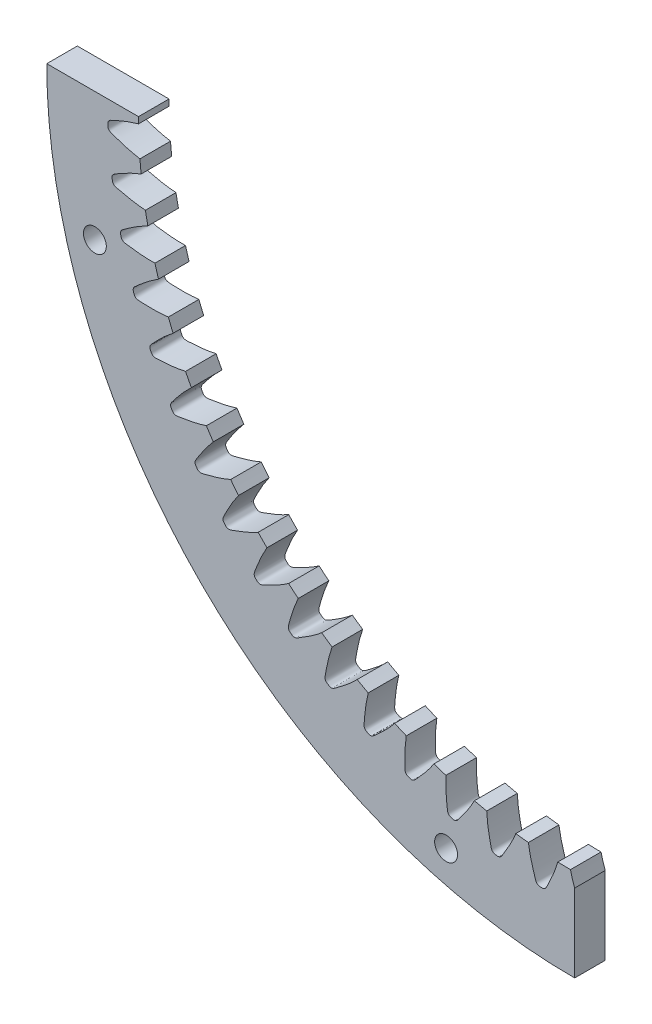
SolidWorks part; units mm, degrees
material "Д16 ГОСТ 4784-97"
ref_plane "FRONT" through (0, 0, 0) normal (0, 0, 1) x (1, 0, 0)
ref_plane "TOP" through (0, 0, 0) normal (0, 1, 0) x (1, 0, 0)
ref_plane "RIGHT" through (0, 0, 0) normal (1, 0, 0) x (0, 0, -1)
ref_axis "Ось1" through (0, 0, 50) along (0, 0, -1)
sketch "SketchRevolveSpurGear" plane through (0, 0, 0) normal (1, 0, 0) x (0, 0, -1)
  line L0 (0, 0) -> (1, 0) construction
  line L1 (1, 57.078) -> (1, 69.078)
  line L2 (1, 69.078) -> (5, 69.078)
  line L3 (5, 69.078) -> (5, 57.078)
  line L4 (5, 57.078) -> (1, 57.078)
  dimension "MinorDiameter" = 57.078
  dimension "D1" = 12
  dimension "D2" = 4
revolve "SpurGear" add sketch "SketchRevolveSpurGear" angle 360 about L0
sketch "SketchToothSpurGear" plane through (0, 0, 0) normal (0, 0, 1) x (1, 0, 0)
  arc A0 (56.7163, -2.001) -> (56.7163, 2.001) centre (0, 0) ccw
  spline S0 degree 3 poles (56.7163, 2.001) (56.9243, 1.9614) (57.2489, 1.8911) (57.6972, 1.7784) (58.0734, 1.6747) (58.475, 1.554) (58.9015, 1.4154) (59.3516, 1.2564) (59.8273, 1.0806) (60.3419, 0.8578) (60.7493, 0.7297) (60.9671, 0.5733) (61.0225, 0.5178) (61.0697, 0.4552) (61.1072, 0.3864) (61.1437, 0.2896) (61.1566, 0.1851) (61.1546, 0.0805) (61.1552, 0) (61.1546, -0.0805) (61.1566, -0.1851) (61.1437, -0.2896) (61.1072, -0.3864) (61.0697, -0.4552) (61.0225, -0.5178) (60.9671, -0.5733) (60.7493, -0.7297) (60.3419, -0.8578) (59.8273, -1.0806) (59.3516, -1.2564) (58.9015, -1.4154) (58.475, -1.554) (58.0734, -1.6747) (57.6972, -1.7784) (57.2489, -1.8911) (56.9243, -1.9614) (56.7163, -2.001) knots 0 0 0 0 0.061975 0.097219 0.135299 0.176217 0.219972 0.266564 0.315993 0.36826 0.43124 0.438862 0.446485 0.454108 0.461731 0.469354 0.484283 0.492142 0.5 0.507858 0.515717 0.530646 0.538269 0.545892 0.553515 0.561138 0.56876 0.63174 0.684007 0.733436 0.780028 0.823783 0.864701 0.902781 0.938025 1 1 1 1
extrude "ToothExtrudeCutSpurGear" cut sketch "SketchToothSpurGear" against normal blind 5 and the other way blind 5
pattern_circular "PatternSpurGear" count 65 over 360 about axis through (0, 0, 50) along (0, 0, -1) of "ToothExtrudeCutSpurGear"
sketch "AuxiliarySketchSpurGear" plane through (0, 0, 0) normal (0, 0, 1) x (1, 0, 0)
  circle A0 centre (0, 0) radius 58.89 construction
  circle A1 centre (0, 0) radius 55.3385 construction
  circle A2 centre (0, 0) radius 61.155 construction
  circle A3 centre (0, 0) radius 57.078 construction
  dimension "PitchDiameter" = 117.78
  dimension "BaseDiameter" = 110.677
  dimension "MajorDiameter" = 122.31
  dimension "MinorDiameter" = 114.156
sketch "Эскиз4" plane through (0, 0, -5) normal (0, 0, -1) x (-1, 0, 0)
  line L0 (78.8039, 0) -> (78.8039, 98.2116)
  line L1 (0, 0) -> (78.8039, 0)
  line L2 (0, 0) -> (0, -72.2075)
  line L5 (78.8039, 98.2116) -> (-105.3357, 98.2116)
  line L6 (-105.3357, 98.2116) -> (-105.3357, -72.2075)
  line L7 (-105.3357, -72.2075) -> (0, -72.2075)
extrude "Вырез-Вытянуть2" cut sketch "Эскиз4" against normal through all
sketch "Эскиз5" plane through (0, 0, -5) normal (0, 0, -1) x (-1, 0, 0)
  line L0 (0, 0) -> (48.8455, -48.8455) construction
  line L1 (0, -69.078) -> (0, -58.89) construction
  arc A1 (0, -65) -> (16.8232, -62.7852) centre (0, 0) ccw construction
  circle A2 centre (16.8232, -62.7852) radius 1.5
  arc A3 (0, -69.078) -> (69.078, 0) centre (0, 0) ccw construction
  circle A4 centre (62.7852, -16.8232) radius 1.5
  dimension "D1" = 65
  dimension "D3" = 3
  dimension "D2" = 45
extrude "Вырез-Вытянуть3" cut sketch "Эскиз5" against normal through all
